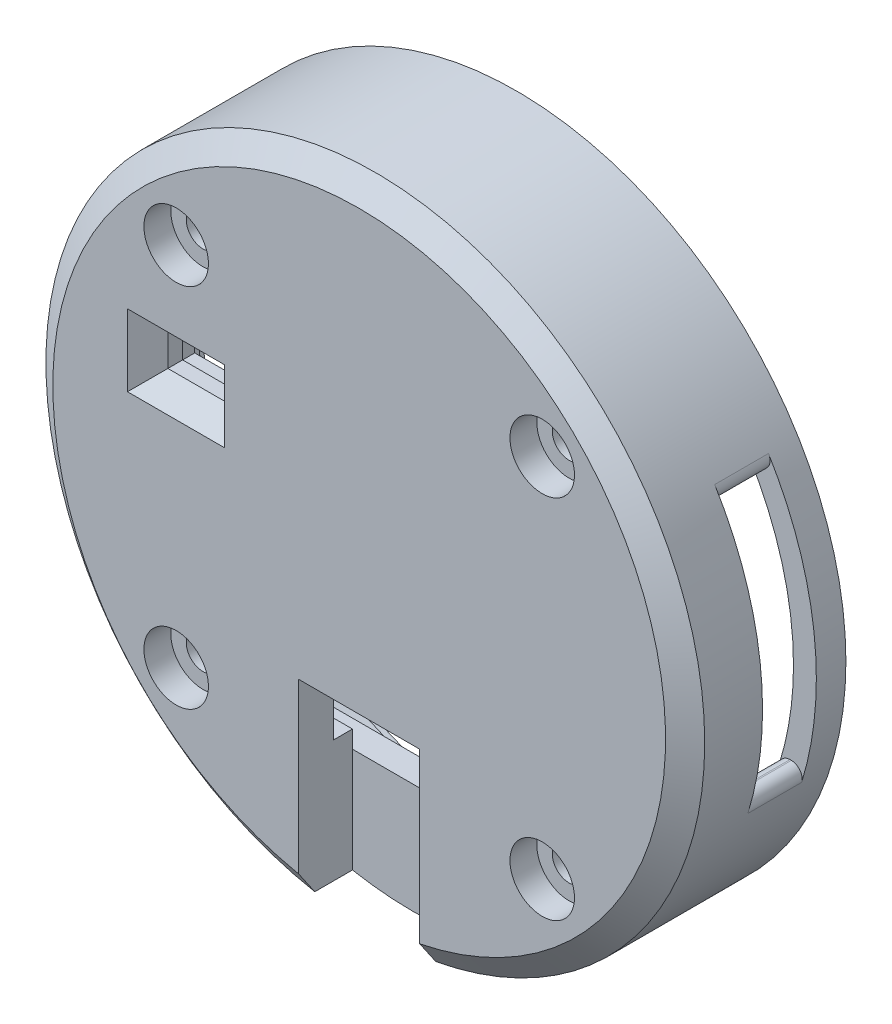
SolidWorks part; units mm, degrees
material "可锻铸铁"
ref_plane "前视基准面" through (0, 0, 0) normal (0, 0, 1) x (1, 0, 0)
ref_plane "上视基准面" through (0, 0, 0) normal (0, 1, 0) x (1, 0, 0)
ref_plane "右视基准面" through (0, 0, 0) normal (1, 0, 0) x (0, 0, -1)
sketch "草图2" plane through (0, 0, 0) normal (0, 0, 1) x (1, 0, 0)
  line L0 (-36.168, 0) -> (40.0746, 0) construction
  line L1 (0, -37.0248) -> (0, 41.4439) construction
  line L2 (-18.291, -16.3) -> (18.291, -16.3)
  line L3 (0, 0) -> (19.8165, 19.8165) construction
  line L4 (-4.5, -9.8) -> (4.5, -9.8)
  line L5 (4.5, -9.8) -> (4.5, -24.0832)
  line L6 (-4.5, -9.8) -> (-4.5, -24.0832)
  line L7 (-17.1709, -15) -> (-15.8102, -15)
  line L8 (-11.4134, -15) -> (11.4134, -15)
  line L9 (2.9, -19.25) -> (-2.9, -19.25)
  line L10 (15.8102, -15) -> (17.1709, -15)
  line L11 (19.6873, 11.5) -> (21.6333, 11.5)
  line L12 (21.9408, -6.2) -> (23.7025, -6.2)
  line L13 (-15.7305, 6.2) -> (-15.7305, 3.8561)
  line L14 (-15.7305, 3.8561) -> (-11.5305, 3.8561)
  line L15 (-11.5305, 3.8561) -> (-11.5305, 6.2)
  line L16 (-11.5305, 6.2) -> (-15.7305, 6.2)
  line L17 (-8.7486, 5.028) -> (-18.3313, 5.028) construction
  line L18 (-16.2305, 3.3561) -> (-16.2305, 6.7)
  line L19 (-16.2305, 6.7) -> (-9.5305, 6.7)
  line L20 (-9.5305, 6.7) -> (-9.5305, 3.3561)
  line L21 (-17.2305, 7.7) -> (-17.2305, 2.3561)
  line L22 (-17.2305, 7.7) -> (-8.5305, 7.7)
  line L23 (-8.5305, 7.7) -> (-8.5305, 2.3561)
  line L24 (-17.2305, 2.3561) -> (-8.5305, 2.3561)
  line L25 (-16.2305, 3.3561) -> (-9.5305, 3.3561)
  line L26 (-3.766, -20.75) -> (-2.6733, -22.6427)
  line L27 (3.766, -20.75) -> (2.6733, -22.6427)
  circle A0 centre (0, 0) radius 24.5
  circle A2 centre (0, 0) radius 23.6
  circle A6 centre (0, 0) radius 19.25 construction
  circle A7 centre (0, 0) radius 22.8
  circle A8 centre (13.6118, 13.6118) radius 1.25
  circle A9 centre (13.6118, -13.6118) radius 1.25
  circle A10 centre (-13.6118, -13.6118) radius 1.25
  circle A11 centre (-13.6118, 13.6118) radius 1.25
  circle A12 centre (-13.6118, 13.6118) radius 2.6
  circle A13 centre (13.6118, 13.6118) radius 2.6
  circle A14 centre (13.6118, -13.6118) radius 2.6
  circle A15 centre (-13.6118, -13.6118) radius 2.6
  circle A16 centre (-13.6118, 13.6118) radius 2.4
  circle A17 centre (13.6118, 13.6118) radius 2.4
  circle A18 centre (13.6118, -13.6118) radius 2.4
  circle A19 centre (-13.6118, -13.6118) radius 2.4
  arc A20 (-2.9, -19.25) -> (-3.766, -20.75) centre (-2.9, -20.25) ccw
  arc A21 (2.9, -19.25) -> (3.766, -20.75) centre (2.9, -20.25) cw
  point P24 (0, 0)
  point P25 (0, -9.8)
  point P32 (0, 0)
  point P39 (0, 0)
  point P57 (0, 0)
  point P62 (-11.5305, 5.028)
  point P70 (-9.5305, 5.028)
  point P71 (-8.5305, 5.028)
  point P72 (-17.2305, 5.028)
  point P73 (-16.2305, 5.028)
  point P80 (0, -19.25)
  dimension "D1" = 47.2
  dimension "D2" = 49
  dimension "D3" = 2.5
  dimension "D5" = 45.6
  dimension "D9" = 45
  dimension "D4" = 38.5
  dimension "D10" = 4
  dimension "D12" = 5.2
  dimension "D16" = 4.8
  dimension "D27" = 4.2
  dimension "D28" = 2.9
  dimension "D30" = 1
  dimension "D6" = 4.5
  dimension "D7" = 9.8
  dimension "D8" = 16.3
  dimension "D11" = 15
  dimension "D14" = 6.2
  dimension "D15" = 11.5
  dimension "D18" = 3.8561
  dimension "D19" = 11.5305
  dimension "D20" = 2.3439
  dimension "D21" = 0.5
  dimension "D22" = 2
  dimension "D23" = 1
  dimension "D24" = 1
  dimension "D25" = 0.5
  dimension "D26" = 1
  dimension "D29" = 60
  dimension "D13" = 4
  dimension "D17" = 4
extrude "凸台-拉伸3" add sketch "草图2" against normal blind 11.7 contours A2 L11 A0 L2 | A2 L12 A0 L11 | A2 L2 A0 L12 | A2 L5 A0 L2 | A2 L6 A0 L5 | A2 L2 A0 L6 region at (-13.6482, 19.6005, 0) region at (-11.4891, -20.6732, 0) region at (23.5967, 5.8821, 0) region at (0, -23.9082, 0) region at (11.4891, -20.6732, 0) region at (20.8674, -11.475, 0)
extrude "凸台-拉伸4" add sketch "草图2<5>" against normal blind 10.7 contours A7 L2 A2 L6 | A7 L11 A2 L2 | A7 L12 A2 L11 | A7 L2 A2 L12 | A7 L5 A2 L2 | A7 L6 A2 L5 region at (-13.6588, 18.5106, 0) region at (-10.8323, -20.1347, 0) region at (22.6644, 5.8957, 0) region at (0, -23.0529, 0) region at (10.8323, -20.1347, 0) region at (19.8607, -11.499, 0)
sketch "草图2<5>" plane through (0, 0, 0) normal (0, 0, 1) x (1, 0, 0) same geometry as "草图2"
extrude "凸台-拉伸5" add sketch "草图2<6>" against normal blind 2.6 contours A10 L7 L6 L4 L5 A9 A7 A11 A8 | L21 L24 L23 L22 L25 L18 L19 L20 | L18 L25 L20 L19 L16 L15 L14 L13 region at (0.4691, 2.8239, 0) region at (-16.1556, 5.028, 0) region at (-12.8805, 7.5979, 0)
sketch "草图2<6>" plane through (0, 0, 0) normal (0, 0, 1) x (1, 0, 0) same geometry as "草图2"
extrude "凸台-拉伸6" add sketch "草图2<7>" against normal blind 4 contours A15 L7 A7 L2 L6 | A14 L8 L5 L2 A7 L10 region at (-9.5744, -15.684, 0) region at (9.5744, -15.684, 0)
sketch "草图2<7>" plane through (0, 0, 0) normal (0, 0, 1) x (1, 0, 0) same geometry as "草图2"
extrude "凸台-拉伸7" add sketch "草图2<9>" against normal blind 4 contours A12 A11 | A13 A8 | A12 A16 | A13 A17 | A14 A18 | A15 A19 | A19 A10 | A18 A9 | L21 L24 L23 L22 L25 L18 L19 L20 region at (-14.3139, -11.1849, 0) region at (12.9097, -11.1849, 0) region at (-12.8805, 7.5979, 0) region at (-16.1383, 13.6118, 0) region at (11.0853, 13.6118, 0) region at (-15.9439, 13.6118, 0) region at (11.2797, 13.6118, 0) region at (11.2797, -13.6118, 0) region at (-15.9439, -13.6118, 0)
sketch "草图2<9>" plane through (0, 0, 0) normal (0, 0, 1) x (1, 0, 0) same geometry as "草图2"
extrude "凸台-拉伸8" add sketch "草图2<11>" against normal blind 6 contours L5 A7 L2 | L6 A7 L5 L2 | L2 A7 L6 region at (-8.71, -18.5721, 0) region at (0, -18.4439, 0) region at (8.71, -18.5721, 0)
sketch "草图2<11>" plane through (0, 0, 0) normal (0, 0, 1) x (1, 0, 0) same geometry as "草图2"
extrude "凸台-拉伸10" add sketch "草图2<17>" against normal blind 8.6 contours A21 L9 A20 L26 A7 L27 region at (0, -20.9067, 0)
sketch "草图2<17>" plane through (0, 0, 0) normal (0, 0, 1) x (1, 0, 0) same geometry as "草图2"
extrude "切除-拉伸1" cut sketch "草图2<10>" against normal blind 4 contours L6 A7 L5 L2 | A7 L6 A2 L5 | A2 L6 A0 L5 | A21 L9 A20 L26 A7 L27 region at (0, -23.9082, 0) region at (0, -23.0529, 0) region at (0, -18.4439, 0) region at (0, -20.9067, 0)
sketch "草图2<10>" plane through (0, 0, 0) normal (0, 0, 1) x (1, 0, 0) same geometry as "草图2"
extrude "切除-拉伸2" cut sketch "草图2<13>" against normal blind 9.5 contours A2 L12 A0 L11 | A7 L12 A2 L11 region at (23.5967, 5.8821, 0) region at (22.6644, 5.8957, 0)
sketch "草图2<13>" plane through (0, 0, 0) normal (0, 0, 1) x (1, 0, 0) same geometry as "草图2"
extrude "凸台-拉伸9" add sketch "草图2<14>" against normal blind 5.5 contours A2 L12 A0 L11 | A7 L12 A2 L11 region at (23.5967, 5.8821, 0) region at (22.6644, 5.8957, 0)
sketch "草图2<14>" plane through (0, 0, 0) normal (0, 0, 1) x (1, 0, 0) same geometry as "草图2"
extrude "切除-拉伸3" cut sketch "草图2<15>" against normal blind 2 contours A16 A11 | A17 A8 | A18 A9 | A19 A10 region at (-15.9439, 13.6118, 0) region at (11.2797, 13.6118, 0) region at (11.2797, -13.6118, 0) region at (-15.9439, -13.6118, 0)
sketch "草图2<15>" plane through (0, 0, 0) normal (0, 0, 1) x (1, 0, 0) same geometry as "草图2"
chamfer "倒角2" distance 1.5 angle 45 4 edges at (-13.6305, 3.8561, 0) (-15.7305, 5.028, 0) (-13.6305, 6.2, 0) (-11.5305, 5.028, 0)
fillet "圆角2" radius 0.8 1 edges at (21.6333, 11.5, -7.5)
fillet "圆角3" radius 0.8 1 edges at (23.7025, -6.2, -7.5)
fillet "圆角4" radius 0.8 1 edges at (21.9408, -6.2, -7.5)
fillet "圆角5" radius 0.8 1 edges at (19.6873, 11.5, -7.5)
chamfer "倒角3" distance 1.2 angle 55 1 edges at (0, 24.5, 0) first distance on face at (0, -12.0416, -2)
